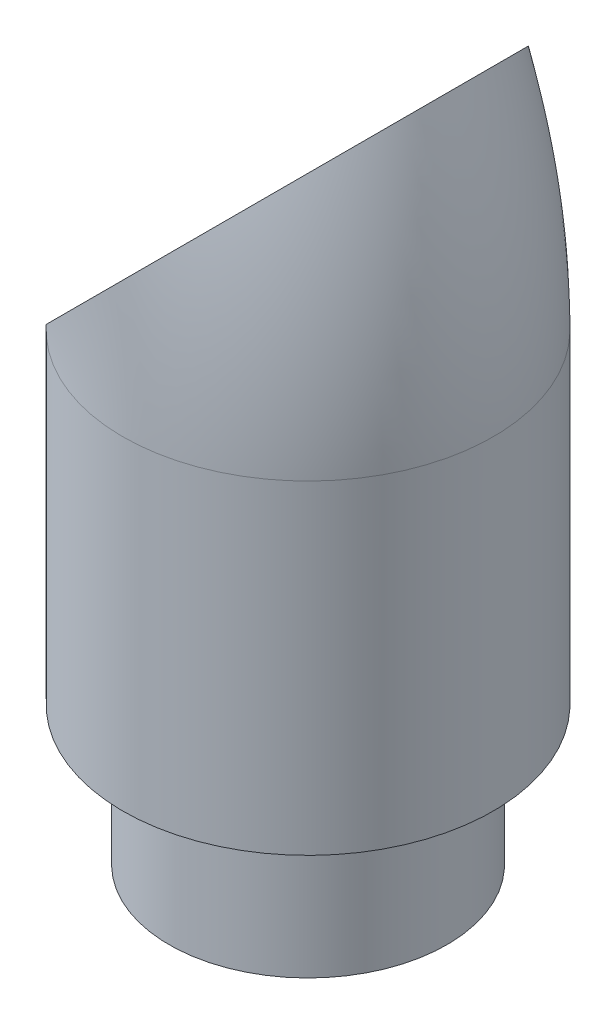
SolidWorks part; units mm, degrees
ref_plane "Front Plane" through (0, 0, 0) normal (0, 0, 1) x (1, 0, 0)
ref_plane "Top Plane" through (0, 0, 0) normal (0, 1, 0) x (1, 0, 0)
ref_plane "Right Plane" through (0, 0, 0) normal (1, 0, 0) x (0, 0, -1)
sketch "Sketch1" plane through (0, 0, 0) normal (0, 1, 0) x (1, 0, 0)
  circle A0 centre (0, 0) radius 4
  dimension "D1" = 8
sketch "Sketch2" plane through (0, 0, 0) normal (0, 0, 1) x (1, 0, 0)
  line L0 (0, 0) -> (0, 10)
  line L1 (-10, 20) -> (-20, 20)
  arc A0 (-10, 20) -> (0, 10) centre (-10, 10) cw
  dimension "D3" = 10
  dimension "D1" = 10
  dimension "D2" = 10
sweep "Sweep1" add profiles "Sketch1" path "Sketch2"
sketch "Sketch3" plane through (0, 0, 0) normal (0, -1, 0) x (1, 0, 0)
  circle A0 centre (0, 0) radius 3
  circle A2 centre (0, 0) radius 4
  circle A3 centre (0, 0) radius 4
  dimension "D1" = 6
  dimension "D2" = 0
extrude "Cut-Extrude1" cut sketch "Sketch3" against normal blind 3
sketch "Sketch4" plane through (-20, 0, 0) normal (-1, 0, 0) x (0, 0, 1)
  circle A0 centre (0, 20) radius 3
  circle A1 centre (0, 20) radius 4
  circle A2 centre (0, 20) radius 4
  dimension "D2" = 6
  dimension "D1" = 0
extrude "Cut-Extrude2" cut sketch "Sketch4" against normal blind 3
sketch "Sketch5" plane through (0, 0, 0) normal (0, -1, 0) x (1, 0, 0)
  circle A0 centre (0, 0) radius 1.6
  dimension "D1" = 3.2
extrude "Cut-Extrude3" cut sketch "Sketch5" against normal blind 10
sketch "Sketch6" plane through (-20, 0, 0) normal (-1, 0, 0) x (0, 0, 1)
  circle A0 centre (0, 20) radius 1.6
  dimension "D1" = 3.2
extrude "Cut-Extrude4" cut sketch "Sketch6" against normal blind 10
ref_plane "Plane1" through (-20, 0, 0) normal (-1, 0, 0) x (0, 0, 1)
ref_axis "Axis1" through (-20, 0, -4.6568) along (0, 0, 1)
ref_plane "Plane2" through (-10, 10, 0) normal (-0.7071, 0.7071, 0) x (0, 0, 1)
sketch "Sketch11" plane through (0, 0, 0) normal (0, 0, 1) x (1, 0, 0)
  line L0 (0, 0) -> (0, 34.4839) construction
  line L1 (-20, 20) -> (22.7029, 20) construction
  line L2 (-20, 23) -> (-20, 17) construction
  line L3 (0, 20) -> (-20.3098, -0.3098) construction
  line L4 (-15.0765, 11.9945) -> (5.143, 32.214)
  line L5 (5.143, 32.214) -> (12.214, 25.143)
  line L6 (12.214, 25.143) -> (-8.0055, 4.9235)
  line L7 (-8.0055, 4.9235) -> (-15.0765, 11.9945)
  dimension "D1" = 45
  dimension "D2" = 5
  dimension "D3" = 5
extrude "Cut-Extrude5" cut sketch "Sketch11" against normal through all both and the other way through all
sketch "Sketch14" plane through (-6.4645, 6.4645, 0) normal (-0.7071, 0.7071, 0) x (0, 0, 1)
  circle A0 centre (0, 9.1421) radius 1.5
  ellipse E1 centre (0, 9.1421) end of major axis (0, 14.799) minor radius 4 (-2.7242, 5) -> (2.7242, 5) ccw
  ellipse E2 centre (0, 9.1421) end of major axis (0, 14.799) minor radius 4 (-2.7242, 5) -> (2.7242, 5) ccw
  spline S1 degree 3 poles (-3581.4002, 1777.903) (-393.8196, 122.4592) (-14.7991, -32.1165) (3.596, 6.5188) (3.746, 6.9401) (3.947, 7.7913) (4.0004, 8.224) (3.9998, 8.8849) (3.9857, 9.1076) (3.9293, 9.5438) (3.887, 9.7588) (3.7728, 10.1826) (3.7003, 10.3928) (3.5255, 10.7996) (3.4243, 10.9942) (3.194, 11.3657) (3.0649, 11.5426) (2.7769, 11.8774) (2.6178, 12.0347) (2.2813, 12.3165) (2.1024, 12.4428) (1.7227, 12.6653) (1.52, 12.7619) (1.1072, 12.9159) (0.8958, 12.9745) (0.4628, 13.0544) (0.2392, 13.0755) (-0.2017, 13.0778) (-0.4206, 13.0595) (-0.8552, 12.9843) (-1.0722, 12.9265) (-1.4865, 12.7765) (-1.686, 12.684) (-2.0696, 12.4645) (-2.2537, 12.3369) (-2.5938, 12.057) (-2.7515, 11.9037) (-3.043, 11.5709) (-3.1762, 11.3914) (-3.4108, 11.0187) (-3.5134, 10.8241) (-3.6904, 10.4191) (-3.7646, 10.2083) (-3.8815, 9.7835) (-3.925, 9.5679) (-3.9837, 9.131) (-3.9988, 8.9082) (-4.0022, 8.2458) (-3.9503, 7.8091) (-3.748, 6.945) (-3.6006, 6.5301) (9.0159, -20.08) (206.4321, 20.7572) (-789.8558, 3920.1741) knots -5.980044 -5.980044 -5.980044 -5.980044 0.0625 0.0625 0.125 0.125 0.1875 0.1875 0.21875 0.21875 0.25 0.25 0.28125 0.28125 0.3125 0.3125 0.34375 0.34375 0.375 0.375 0.40625 0.40625 0.4375 0.4375 0.46875 0.46875 0.5 0.5 0.53125 0.53125 0.5625 0.5625 0.59375 0.59375 0.625 0.625 0.65625 0.65625 0.6875 0.6875 0.71875 0.71875 0.75 0.75 0.78125 0.78125 0.8125 0.8125 0.875 0.875 0.9375 0.9375 5.060224 5.060224 5.060224 5.060224 only from (2.7242, 5) to (-2.7242, 5)
  spline S2 degree 3 poles (2.7242, 5) (2.9924, 5.3528) (3.2194, 5.7277) (3.596, 6.5188) (3.746, 6.9401) (3.947, 7.7913) (4.0004, 8.224) (3.9998, 8.8849) (3.9857, 9.1076) (3.9293, 9.5438) (3.887, 9.7588) (3.7728, 10.1826) (3.7003, 10.3928) (3.5255, 10.7996) (3.4243, 10.9942) (3.194, 11.3657) (3.0649, 11.5426) (2.7769, 11.8774) (2.6178, 12.0347) (2.2813, 12.3165) (2.1024, 12.4428) (1.7227, 12.6653) (1.52, 12.7619) (1.1072, 12.9159) (0.8958, 12.9745) (0.4628, 13.0544) (0.2392, 13.0755) (-0.2017, 13.0778) (-0.4206, 13.0595) (-0.8552, 12.9843) (-1.0722, 12.9265) (-1.4865, 12.7765) (-1.686, 12.684) (-2.0696, 12.4645) (-2.2537, 12.3369) (-2.5938, 12.057) (-2.7515, 11.9037) (-3.043, 11.5709) (-3.1762, 11.3914) (-3.4108, 11.0187) (-3.5134, 10.8241) (-3.6904, 10.4191) (-3.7646, 10.2083) (-3.8815, 9.7835) (-3.925, 9.5679) (-3.9837, 9.131) (-3.9988, 8.9082) (-4.0022, 8.2458) (-3.9503, 7.8091) (-3.748, 6.945) (-3.6006, 6.5301) (-3.2238, 5.7353) (-2.9928, 5.3534) (-2.7242, 5) knots 0 0 0 0 0.0625 0.0625 0.125 0.125 0.1875 0.1875 0.21875 0.21875 0.25 0.25 0.28125 0.28125 0.3125 0.3125 0.34375 0.34375 0.375 0.375 0.40625 0.40625 0.4375 0.4375 0.46875 0.46875 0.5 0.5 0.53125 0.53125 0.5625 0.5625 0.59375 0.59375 0.625 0.625 0.65625 0.65625 0.6875 0.6875 0.71875 0.71875 0.75 0.75 0.78125 0.78125 0.8125 0.8125 0.875 0.875 0.9375 0.9375 1 1 1 1 construction
  dimension "D2" = 3
  dimension "D1" = 0
extrude "Boss-Extrude4" add sketch "Sketch14" along normal blind 10 contours A0
sketch "Sketch15" plane through (-6.4645, 6.4645, 0) normal (-0.7071, 0.7071, 0) x (0, 0, 1)
  line L1 (-37.7925, 35.4298) -> (44.5146, 35.4298)
  line L2 (-37.7925, 35.4298) -> (-37.7925, -23.2939)
  line L3 (-37.7925, -23.2939) -> (44.5146, -23.2939)
  line L4 (44.5146, 35.4298) -> (44.5146, -23.2939)
extrude "Cut-Extrude6" cut sketch "Sketch15" along normal through all
